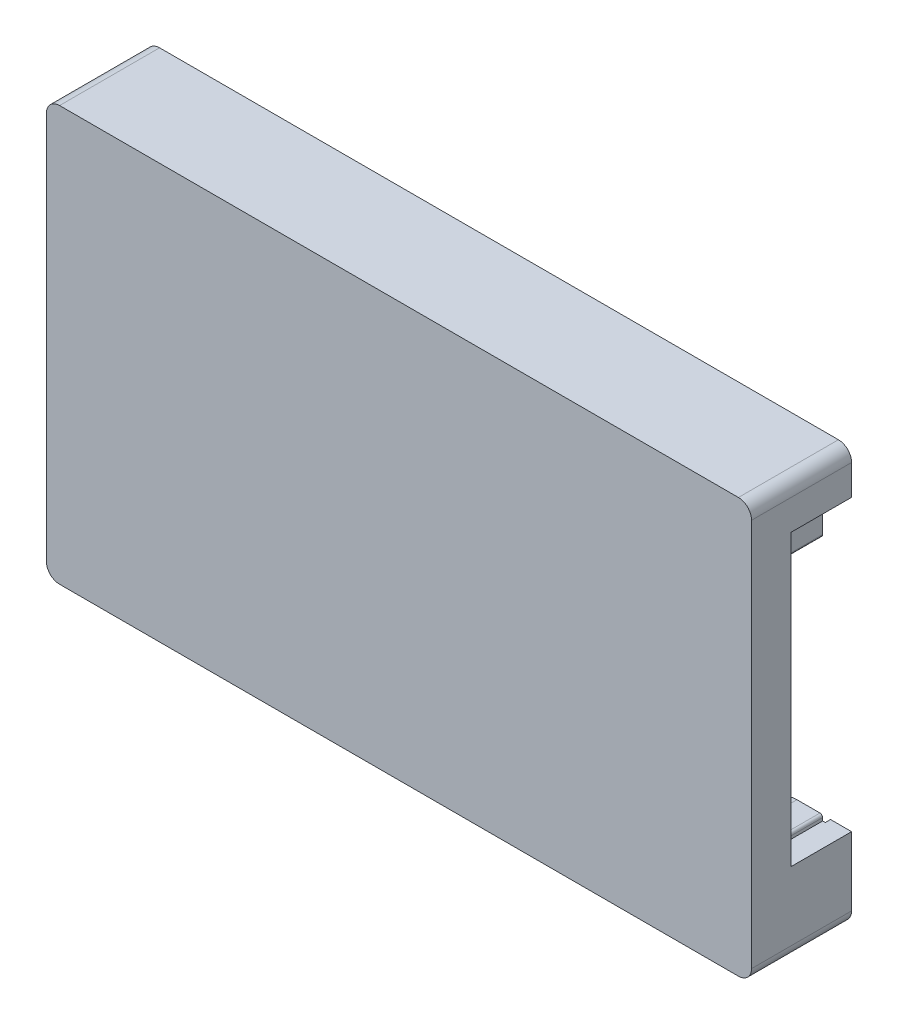
SolidWorks part; units mm, degrees
ref_plane "Спереди" through (0, 0, 0) normal (0, 0, 1) x (1, 0, 0)
ref_plane "Сверху" through (0, 0, 0) normal (0, 1, 0) x (1, 0, 0)
ref_plane "Справа" through (0, 0, 0) normal (1, 0, 0) x (0, 0, -1)
sketch "Эскиз1" plane through (0, 0, 0) normal (0, 0, 1) x (1, 0, 0)
  line L0 (5.383, 29.905) -> (5.383, 1.6) construction
  line L1 (0, 0) -> (53.584, 0)
  line L2 (0, 0) -> (0, 31.505)
  line L3 (0, 31.505) -> (53.584, 31.505)
  line L4 (53.584, 0) -> (53.584, 31.505)
  line L5 (1.2, 1.6) -> (51.984, 1.6)
  line L6 (1.2, 1.6) -> (1.2, 29.905)
  line L7 (1.2, 29.905) -> (51.984, 29.905)
  line L8 (51.984, 1.6) -> (51.984, 29.905)
  line L9 (49.833, 29.905) -> (49.833, 1.6) construction
  line L10 (1.2, 26.865) -> (51.984, 26.865) construction
  line L11 (1.2, 4.64) -> (51.984, 4.64) construction
  line L12 (7.383, 26.865) -> (7.383, 29.905)
  line L13 (5.383, 24.865) -> (1.2, 24.865)
  line L14 (5.383, 6.64) -> (1.2, 6.64)
  line L15 (7.383, 4.64) -> (7.383, 1.6)
  line L16 (47.833, 26.865) -> (47.833, 29.905)
  line L17 (49.833, 24.865) -> (51.984, 24.865)
  line L18 (51.984, 28.213) -> (53.584, 28.213)
  line L19 (51.984, 6.213) -> (53.584, 6.213)
  line L20 (49.833, 6.64) -> (51.984, 6.64)
  line L21 (47.833, 4.64) -> (47.833, 1.6)
  line L22 (1.2, 20.5525) -> (0, 20.5525)
  line L23 (1.2, 10.9525) -> (0, 10.9525)
  circle A0 centre (5.383, 26.865) radius 0.7
  circle A1 centre (5.383, 4.64) radius 0.7
  circle A2 centre (49.833, 26.865) radius 0.7
  circle A3 centre (49.833, 4.64) radius 0.7
  circle A4 centre (5.383, 26.865) radius 2
  circle A5 centre (5.383, 4.64) radius 2
  circle A6 centre (49.833, 26.865) radius 2
  circle A7 centre (49.833, 4.64) radius 2
  point P53 (1.2, 15.7525)
  dimension "D11" = 1.4
  dimension "D12" = 1.4
  dimension "D13" = 1.4
  dimension "D14" = 1.4
  dimension "D15" = 4
  dimension "D16" = 4
  dimension "D17" = 4
  dimension "D18" = 4
  dimension "D1" = 1.6
  dimension "D2" = 1.6
  dimension "D3" = 28.305
  dimension "D4" = 1.2
  dimension "D5" = 1.6
  dimension "D6" = 50.784
  dimension "D7" = 48.633
  dimension "D8" = 25.265
  dimension "D9" = 4.183
  dimension "D10" = 3.04
  dimension "D19" = 4.613
  dimension "D20" = 22
  dimension "D21" = 4.8
  dimension "D22" = 4.8
extrude "Бобышка-Вытянуть5" add sketch "Эскиз1" against normal blind 3 contours A7 L20 L8 L17 A6 L16 L7 L12 A4 L13 L6 L14 A5 L15 L5 L21 | L8 L19 L4 L18 | A1 | A0 | A3 | A2 | A6 L17 L8 L7 L16 | A6 A2 | A4 L12 L7 L6 L13 | A4 A0 | A5 L14 L6 L5 L15 | A5 A1 | A7 L21 L5 L8 L20 | A7 A3 region at (52.784, 17.213, 0) region at (26.9045, 15.7525, 0) region at (51.9187, 3.9065, 0) region at (3.3902, 3.6513, 0) region at (51.9187, 26.539, 0) region at (3.3902, 27.8537, 0) region at (6.7572, 6.0142, 0) region at (51.2072, 6.0142, 0) region at (4.0088, 28.2392, 0) region at (48.4588, 25.4908, 0) region at (5.383, 26.865, 0) region at (5.383, 4.64, 0) region at (49.833, 26.865, 0) region at (49.833, 4.64, 0)
extrude "Бобышка-Вытянуть6" add sketch "Эскиз1<7>" against normal blind 7.6 contours L22 L6 L7 L8 L18 L4 L3 L2 | L6 L23 L2 L1 L4 L19 L8 L5 region at (0.5469, 5.4762, 0) region at (24.5486, 30.0436, 0)
sketch "Эскиз1<7>" plane through (0, 0, 0) normal (0, 0, 1) x (1, 0, 0) same geometry as "Эскиз1"
extrude "Бобышка-Вытянуть7" add sketch "Эскиз1<8>" against normal blind 7.2 contours A6 L17 L8 L7 L16 | A6 A2 | A4 L12 L7 L6 L13 | A4 A0 | A7 L21 L5 L8 L20 | A7 A3 | A5 L14 L6 L5 L15 | A5 A1 region at (51.9187, 3.9065, 0) region at (3.3902, 3.6513, 0) region at (51.9187, 26.539, 0) region at (3.3902, 27.8537, 0) region at (6.7572, 6.0142, 0) region at (51.2072, 6.0142, 0) region at (4.0088, 28.2392, 0) region at (48.4588, 25.4908, 0)
sketch "Эскиз1<8>" plane through (0, 0, 0) normal (0, 0, 1) x (1, 0, 0) same geometry as "Эскиз1"
extrude "Бобышка-Вытянуть8" add sketch "Эскиз1<9>" against normal blind 3.7 contours L23 L6 L22 L2 region at (0.6, 15.7525, 0)
sketch "Эскиз1<9>" plane through (0, 0, 0) normal (0, 0, 1) x (1, 0, 0) same geometry as "Эскиз1"
fillet "Скругление1" radius 1 4 edges at (53.584, 0, -3.8) (0, 0, -3.8) (0, 31.505, -3.8) (53.584, 31.505, -3.8)
sketch "Эскиз2" plane through (0, 0, -3) normal (0, 0, -1) x (-1, 0, 0)
  line L0 (-44.808, 26.865) -> (-35.808, 26.865) construction
  line L1 (-44.808, 28.365) -> (-35.808, 28.365)
  line L2 (-44.808, 25.365) -> (-35.808, 25.365)
  line L3 (-30.33, 26.865) -> (-21.33, 26.865) construction
  line L4 (-30.33, 28.365) -> (-21.33, 28.365)
  line L5 (-30.33, 25.365) -> (-21.33, 25.365)
  line L7 (-1.2, 1.6) -> (-1.2, 6.64) construction
  line L8 (-7.383, 29.905) -> (-47.833, 29.905) construction
  line L9 (-1.2, 6.64) -> (-1.2, 24.865) construction
  line L10 (-7.383, 1.6) -> (-47.833, 1.6) construction
  arc A0 (-44.808, 28.365) -> (-44.808, 25.365) centre (-44.808, 26.865) ccw
  arc A1 (-35.808, 25.365) -> (-35.808, 28.365) centre (-35.808, 26.865) ccw
  arc A2 (-30.33, 28.365) -> (-30.33, 25.365) centre (-30.33, 26.865) ccw
  arc A3 (-21.33, 25.365) -> (-21.33, 28.365) centre (-21.33, 26.865) ccw
  circle A4 centre (-12.876, 4.513) radius 1.5
  point P2 (-40.308, 26.865)
  point P8 (-25.83, 26.865)
  dimension "D8" = 3
  dimension "D2" = 3
  dimension "D3" = 9
  dimension "D4" = 24.63
  dimension "D5" = 3
  dimension "D6" = 9
  dimension "D7" = 39.108
  dimension "D9" = 2.913
  dimension "D10" = 11.676
  dimension "D11" = 3.04
extrude "Вырез-Вытянуть1" cut sketch "Эскиз2" against normal blind 2.4
chamfer "Фаска1" distance 0.8 angle 45 9 edges at (11.376, 4.513, -3) (40.308, 25.365, -3) (34.308, 26.865, -3) (46.308, 26.865, -3) (40.308, 28.365, -3) (25.83, 25.365, -3) (19.83, 26.865, -3) (31.83, 26.865, -3) (25.83, 28.365, -3)
fillet "Скругление2" radius 0.4 2 edges at (0.6, 10.9525, -3.7) (0.6, 20.5525, -3.7)
sketch "Эскиз3" plane through (0, 0, -7.2) normal (0, 0, -1) x (-1, 0, 0)
  line L1 (-51.984, 24.865) -> (-51.784, 24.865)
  line L2 (-51.984, 24.865) -> (-51.984, 28.1203)
  line L3 (-51.984, 28.1203) -> (-51.784, 28.1203)
  line L4 (-51.784, 24.865) -> (-51.784, 28.1203)
  line L5 (-51.984, 6.64) -> (-51.784, 6.64)
  line L6 (-51.984, 6.64) -> (-51.984, 6.213)
  line L7 (-51.984, 6.213) -> (-51.784, 6.213)
  line L8 (-51.784, 6.64) -> (-51.784, 6.213)
  dimension "D1" = 0.2
  dimension "D2" = 0.2
extrude "Вырез-Вытянуть2" cut sketch "Эскиз3" against normal up to surface (4.2 mm away) up to face at (50.533, 4.64, -3)
fillet "Скругление3" radius 0.2 2 edges at (51.784, 6.64, -5.1) (51.784, 24.865, -5.1)
